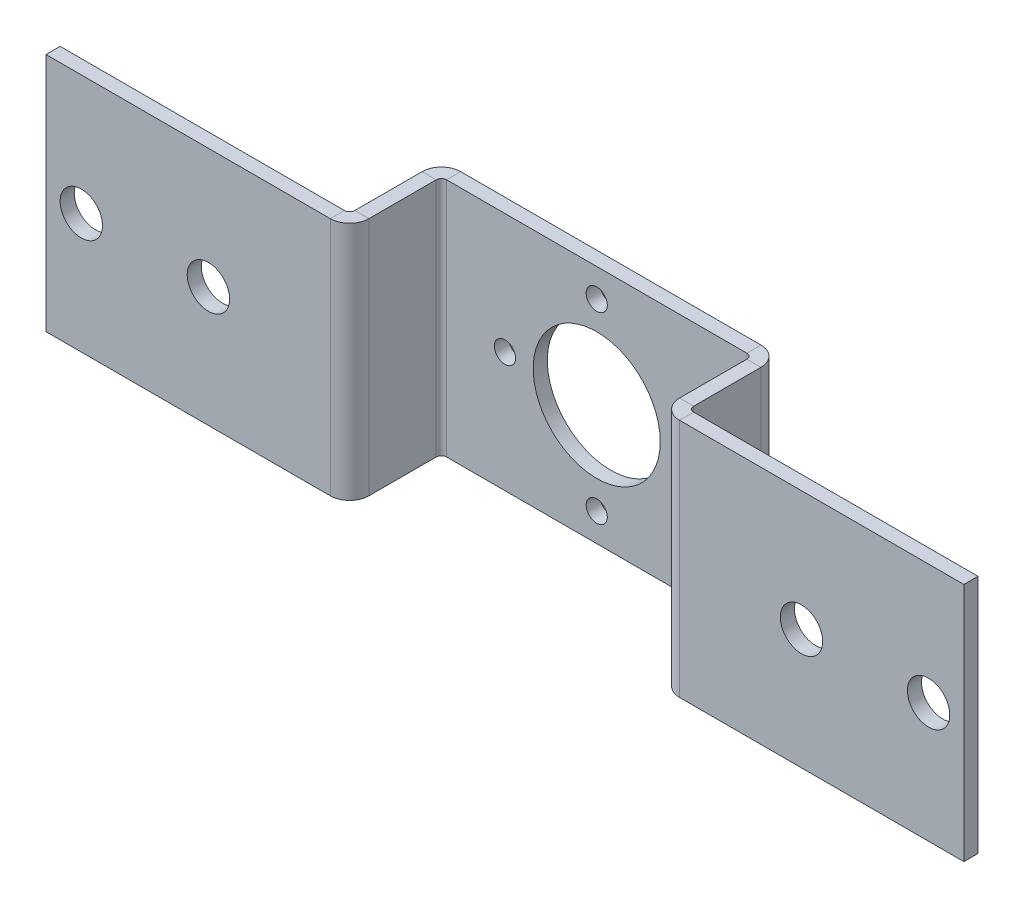
SolidWorks part; units mm, degrees
note: The reader was unsure of these and kept them because the rebuilt part matched: flange length of "Edge-Flange1", "Edge-Flange2".
material "1023 Carbon Steel Sheet (SS)"
ref_plane "Front Plane" through (0, 0, 0) normal (0, 0, 1) x (1, 0, 0)
ref_plane "Top Plane" through (0, 0, 0) normal (0, 1, 0) x (1, 0, 0)
ref_plane "Right Plane" through (0, 0, 0) normal (1, 0, 0) x (0, 0, -1)
sketch "Sketch1" plane through (0, 0, 0) normal (0, 0, 1) x (1, 0, 0)
  line L1 (-22, 17) -> (22, 17)
  line L2 (-22, 17) -> (-22, -17)
  line L3 (-22, -17) -> (22, -17)
  line L4 (22, 17) -> (22, -17)
  line L5 (-22, 17) -> (22, -17) construction
  line L6 (-22, -17) -> (22, 17) construction
  circle A0 centre (0, 0) radius 9
  circle A1 centre (0, 0) radius 13 construction
  circle A2 centre (0, 13) radius 1.5
  circle A3 centre (13, 0) radius 1.5
  circle A4 centre (0, -13) radius 1.5
  circle A5 centre (-13, 0) radius 1.5
  point P0 (0, 0)
  point P20 (0, 0)
  dimension "D3" = 18
  dimension "D4" = 26
  dimension "D5" = 3
  dimension "D1" = 44
  dimension "D2" = 34
  dimension "D6" = 4
base flange "Base-Flange1" sketch "Sketch1" thickness 2 reverse thickness direction no parameters "D1"=0.7366
edge flange "Edge-Flange1" sketch "Sketch10" flange profiles "Sketch10", "Sketch11" flange angle 90 flange length 13 flange position material outside bend radius 0.7366 thickness 2 relief rectangular parameters "D6"=10, "D8"=1
sketch "Sketch10" plane through (-22, 0, 0) normal (-1, 0, 0) x (0, -1, 0)
  line L2 (-17, 0) -> (-17, 11)
  line L3 (-17, 11) -> (17, 11)
  line L4 (17, 11) -> (17, 0)
  line L7 (-17, 0) -> (17, 0) construction
  line L8 (-17, 0) -> (17, 0)
sketch "Sketch11" plane through (22, 0, 0) normal (1, 0, 0) x (0, 1, 0)
  line L0 (-17, 0) -> (17, 0) construction
  line L1 (-17, 0) -> (17, 0)
  line L2 (-17, 0) -> (-17, 11)
  line L3 (-17, 11) -> (17, 11)
  line L4 (17, 11) -> (17, 0)
bend "EdgeBend1" bend radius 0.7366 bend angle 90 parameters "D5"=1
bend "EdgeBend2" bend radius 0.7366 bend angle 90 parameters "D5"=2
edge flange "Edge-Flange2" sketch "Sketch16" flange profiles "Sketch16", "Sketch17" flange angle 90 flange length 43 flange position material outside bend radius 0.7366 thickness 2 relief rectangular parameters "D6"=10, "D8"=1
sketch "Sketch16" plane through (-24, 0, 11) normal (0, 0, 1) x (0, 1, 0)
  line L2 (-17, 0) -> (-17, 41)
  line L3 (-17, 41) -> (17, 41)
  line L4 (17, 41) -> (17, 0)
  line L7 (-17, 0) -> (17, 0) construction
  line L8 (-17, 0) -> (17, 0)
sketch "Sketch17" plane through (24, 0, 11) normal (0, 0, 1) x (0, -1, 0)
  line L0 (-17, 0) -> (17, 0) construction
  line L1 (-17, 0) -> (17, 0)
  line L2 (-17, 0) -> (-17, 41)
  line L3 (-17, 41) -> (17, 41)
  line L4 (17, 41) -> (17, 0)
bend "EdgeBend3" bend radius 0.7366 bend angle 90 parameters "D5"=3
bend "EdgeBend4" bend radius 0.7366 bend angle 90 parameters "D5"=4
sketch "Sketch18" plane through (0, 0, 11) normal (0, 0, -1) x (-1, 0, 0)
  line L0 (0, 0) -> (65, 0) construction
  line L1 (65, 17) -> (65, -17) construction
  line L2 (0, 0) -> (0, 17) construction
  line L3 (-21.2634, 17) -> (21.2634, 17) construction
  circle A0 centre (60, 0) radius 3
  circle A1 centre (42, 0) radius 3
  circle A2 centre (-60, 0) radius 3
  circle A3 centre (-42, 0) radius 3
  dimension "D1" = 6
  dimension "D2" = 6
  dimension "D4" = 18
extrude "Cut-Extrude1" cut sketch "Sketch18" against normal blind 10 normal cut yes
sketch "Bend-Lines1" [suppressed] plane through (0, 0, 0) normal (0, 1, 0) x (1, 0, 0)
sketch "Bounding-Box1" [suppressed] plane through (0, 0, 0) normal (0, 1, 0) x (1, 0, 0)
sheet metal parameters "Sheet-Metal1" thickness 2 parameters "D1"=0.7366
flat pattern "Flat-Pattern1" [suppressed]
sketch "Bend-Lines2" plane through (0, 0, 0) normal (0, 1, 0) x (1, 0, 0)
sketch3d "Bounding-Box2" [suppressed]
  line L0 (22, -17, 0) -> (-22, -17, 0) construction
  line L1 (22, 17, 0) -> (-22, 17, 0) construction
  line L2 (22, -17, 0) -> (22, 17, 0) construction
  line L3 (-22, -17, 0) -> (-22, 17, 0) construction
sheet metal parameters "Sheet-Metal2" thickness 2 parameters "D1"=0.7366
flat pattern "Flat-Pattern1"
sketch "Bend-Lines2" plane through (0, 0, 0) normal (0, 0, 1) x (1, 0, 0)
  line L0 (22.6273, -17) -> (22.6273, 17) construction
  line L1 (-22.6273, 17) -> (-22.6273, -17) construction
  line L2 (22.6273, -17) -> (22.6273, 17) construction
  line L3 (-22.6273, 17) -> (-22.6273, -17) construction
sketch3d "Bounding-Box2" [suppressed]
  line L0 (-32.2546, -17, 0) -> (32.2546, -17, 0) construction
  line L1 (-32.2546, 17, 0) -> (32.2546, 17, 0) construction
  line L2 (-32.2546, -17, 0) -> (-32.2546, 17, 0) construction
  line L3 (32.2546, -17, 0) -> (32.2546, 17, 0) construction
bend of the flat pattern "Flatten-<EdgeBend1>1"
bend of the flat pattern "Flatten-<EdgeBend2>1"
sheet metal parameters "Sheet-Metal3" thickness 2 parameters "D1"=0.7366
flat pattern "Flat-Pattern1"
sketch "Bend-Lines2" plane through (0, 0, 0) normal (0, 0, 1) x (1, 0, 0)
  line L0 (22.6273, -17) -> (22.6273, 17) construction
  line L1 (-22.6273, 17) -> (-22.6273, -17) construction
  line L2 (22.6273, -17) -> (22.6273, 17) construction
  line L3 (-22.6273, 17) -> (-22.6273, -17) construction
  line L4 (32.882, -17) -> (32.882, 17) construction
  line L5 (-32.882, 17) -> (-32.882, -17) construction
  line L6 (32.882, -17) -> (32.882, 17) construction
  line L7 (-32.882, 17) -> (-32.882, -17) construction
sketch3d "Bounding-Box2" [suppressed]
  line L0 (-74.5093, -17, 0) -> (74.5093, -17, 0) construction
  line L1 (-74.5093, 17, 0) -> (74.5093, 17, 0) construction
  line L2 (-74.5093, -17, 0) -> (-74.5093, 17, 0) construction
  line L3 (74.5093, -17, 0) -> (74.5093, 17, 0) construction
bend of the flat pattern "Flatten-<EdgeBend1>1"
bend of the flat pattern "Flatten-<EdgeBend2>1"
bend of the flat pattern "Flatten-<EdgeBend3>1"
bend of the flat pattern "Flatten-<EdgeBend4>1"
sheet metal parameters "Sheet-Metal4" thickness 2 parameters "D1"=0.7366
flat pattern "Flat-Pattern1"
sketch "Bend-Lines2" plane through (0, 0, 0) normal (0, 0, 1) x (1, 0, 0)
  line L0 (22.6273, -17) -> (22.6273, 17) construction
  line L1 (-22.6273, 17) -> (-22.6273, -17) construction
  line L2 (22.6273, -17) -> (22.6273, 17) construction
  line L3 (-22.6273, 17) -> (-22.6273, -17) construction
  line L4 (34.882, -17) -> (34.882, 17) construction
  line L5 (-34.882, 17) -> (-34.882, -17) construction
  line L6 (34.882, -17) -> (34.882, 17) construction
  line L7 (-34.882, 17) -> (-34.882, -17) construction
sketch3d "Bounding-Box2" [suppressed]
  line L0 (-76.5093, -17, 0) -> (76.5093, -17, 0) construction
  line L1 (-76.5093, 17, 0) -> (76.5093, 17, 0) construction
  line L2 (-76.5093, -17, 0) -> (-76.5093, 17, 0) construction
  line L3 (76.5093, -17, 0) -> (76.5093, 17, 0) construction
bend of the flat pattern "Flatten-<EdgeBend1>1"
bend of the flat pattern "Flatten-<EdgeBend2>1"
bend of the flat pattern "Flatten-<EdgeBend3>1"
bend of the flat pattern "Flatten-<EdgeBend4>1"
